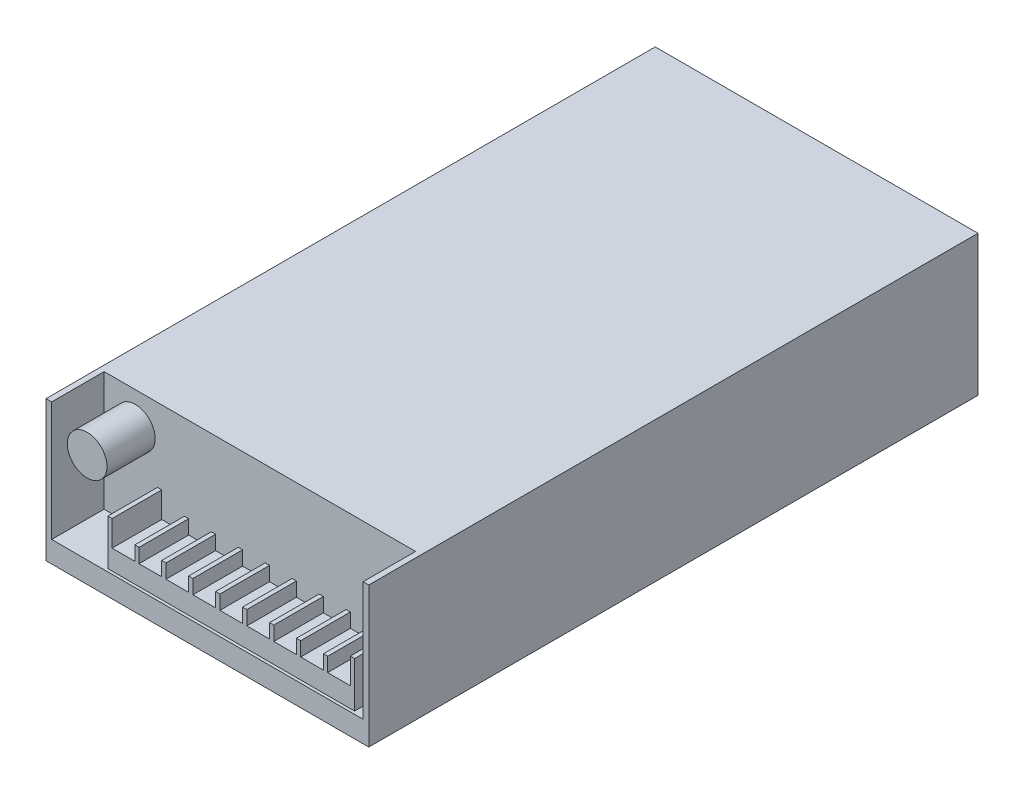
SolidWorks part; units mm, degrees
ref_plane "Front Plane" through (0, 0, 0) normal (0, 0, 1) x (1, 0, 0)
ref_plane "Top Plane" through (0, 0, 0) normal (0, 1, 0) x (1, 0, 0)
ref_plane "Right Plane" through (0, 0, 0) normal (1, 0, 0) x (0, 0, -1)
sketch "Sketch1" plane through (0, 0, 0) normal (0, 1, 0) x (1, 0, 0)
  line L1 (56.9, 107.4) -> (-56.9, 107.4)
  line L2 (56.9, 107.4) -> (56.9, -107.4)
  line L3 (56.9, -107.4) -> (-56.9, -107.4)
  line L4 (-56.9, 107.4) -> (-56.9, -107.4)
  line L5 (56.9, 107.4) -> (-56.9, -107.4) construction
  line L6 (56.9, -107.4) -> (-56.9, 107.4) construction
  point P0 (0, 0)
extrude "Boss-Extrude1" add sketch "Sketch1" along normal blind 49.5
sketch "Sketch2" plane through (0, 49.5, 0) normal (0, 1, 0) x (1, 0, 0)
  line L0 (54.9, -107.4) -> (54.9, -88.9)
  line L1 (-56.9, -107.4) -> (56.9, -107.4) construction
  line L2 (56.9, -107.4) -> (56.9, 107.4) construction
  line L3 (54.9, -88.9) -> (-54.9, -88.9)
  line L4 (-54.9, -88.9) -> (-54.9, -107.4)
  line L5 (-56.9, 107.4) -> (-56.9, -107.4) construction
  line L6 (-54.9, -107.4) -> (54.9, -107.4)
  dimension "D1" = 2
  dimension "D2" = 2
extrude "Cut-Extrude1" cut sketch "Sketch2" against normal blind 42
sketch "Sketch3" plane through (0, 7.5, 0) normal (0, 1, 0) x (1, 0, 0)
  line L0 (54.9, -88.9) -> (50.9, -88.9) construction
  line L1 (54.9, -88.9) -> (-54.9, -88.9) construction
  line L2 (50.9, -88.9) -> (50.9, -106.4)
  line L3 (50.9, -106.4) -> (-36.1, -106.4)
  line L4 (-36.1, -106.4) -> (-36.1, -88.9)
  line L5 (-36.1, -88.9) -> (50.9, -88.9)
  line L6 (-54.9, -107.4) -> (54.9, -107.4) construction
  line L7 (54.9, -107.4) -> (54.9, -88.9) construction
  dimension "D1" = 1
  dimension "D2" = 4
extrude "Boss-Extrude2" add sketch "Sketch3" along normal blind 7
sketch "Sketch4" plane through (0, 14.5, 0) normal (0, 1, 0) x (1, 0, 0)
  line L0 (-36.1, -88.9) -> (-36.1, -106.4)
  line L1 (-36.1, -106.4) -> (-34.6, -106.4)
  line L2 (-36.1, -106.4) -> (50.9, -106.4) construction
  line L3 (-34.6, -106.4) -> (-34.6, -88.9)
  line L4 (50.9, -88.9) -> (-36.1, -88.9) construction
  line L5 (-34.6, -88.9) -> (-36.1, -88.9)
  line L6 (-25.1, -88.9) -> (-26.6, -88.9)
  line L7 (-26.6, -88.9) -> (-26.6, -106.4)
  line L8 (-26.6, -106.4) -> (-25.1, -106.4)
  line L9 (-25.1, -106.4) -> (-25.1, -88.9)
  line L10 (-15.6, -88.9) -> (-17.1, -88.9)
  line L11 (-17.1, -88.9) -> (-17.1, -106.4)
  line L12 (-17.1, -106.4) -> (-15.6, -106.4)
  line L13 (-15.6, -106.4) -> (-15.6, -88.9)
  line L14 (-6.1, -88.9) -> (-7.6, -88.9)
  line L15 (-7.6, -88.9) -> (-7.6, -106.4)
  line L16 (-7.6, -106.4) -> (-6.1, -106.4)
  line L17 (-6.1, -106.4) -> (-6.1, -88.9)
  line L18 (3.4, -88.9) -> (1.9, -88.9)
  line L19 (1.9, -88.9) -> (1.9, -106.4)
  line L20 (1.9, -106.4) -> (3.4, -106.4)
  line L21 (3.4, -106.4) -> (3.4, -88.9)
  line L22 (12.9, -88.9) -> (11.4, -88.9)
  line L23 (11.4, -88.9) -> (11.4, -106.4)
  line L24 (11.4, -106.4) -> (12.9, -106.4)
  line L25 (12.9, -106.4) -> (12.9, -88.9)
  line L26 (22.4, -88.9) -> (20.9, -88.9)
  line L27 (20.9, -88.9) -> (20.9, -106.4)
  line L28 (20.9, -106.4) -> (22.4, -106.4)
  line L29 (22.4, -106.4) -> (22.4, -88.9)
  line L30 (31.9, -88.9) -> (30.4, -88.9)
  line L31 (30.4, -88.9) -> (30.4, -106.4)
  line L32 (30.4, -106.4) -> (31.9, -106.4)
  line L33 (31.9, -106.4) -> (31.9, -88.9)
  line L34 (41.4, -88.9) -> (39.9, -88.9)
  line L35 (39.9, -88.9) -> (39.9, -106.4)
  line L36 (39.9, -106.4) -> (41.4, -106.4)
  line L37 (41.4, -106.4) -> (41.4, -88.9)
  line L38 (50.9, -88.9) -> (49.4, -88.9)
  line L39 (49.4, -88.9) -> (49.4, -106.4)
  line L40 (49.4, -106.4) -> (50.9, -106.4)
  line L41 (50.9, -106.4) -> (50.9, -88.9)
  point P4 (0, 0)
  dimension "D1" = 1.5
  dimension "D2" = 10
extrude "Boss-Extrude3" add sketch "Sketch4" along normal blind 9.05 contours L0 L1 L3 L5 | L41 L38 L39 L40
extrude "Boss-Extrude4" add sketch "Sketch4<3>" along normal blind 5 contours L7 L8 L9 L6 | L11 L12 L13 L10 | L17 L14 L15 L16 | L21 L18 L19 L20 | L23 L24 L25 L22 | L27 L28 L29 L26 | L31 L32 L33 L30 | L35 L36 L37 L34
sketch "Sketch4<3>" plane through (0, 14.5, 0) normal (0, 1, 0) x (1, 0, 0) same geometry as "Sketch4"
sketch "Sketch5" plane through (0, 0, 88.9) normal (0, 0, 1) x (1, 0, 0)
  line L0 (-54.9, 38) -> (-50.9, 38) construction
  line L1 (-54.9, 7.5) -> (-54.9, 49.5) construction
  line L2 (-43.9, 49.5) -> (-43.9, 45) construction
  line L4 (54.9, 49.5) -> (-54.9, 49.5) construction
  circle A0 centre (-43.9, 38) radius 7
  point P10 (0, 0)
  point P11 (0, 0)
  point P12 (0, 0)
  point P13 (0, 0)
  dimension "D1" = 14
  dimension "D2" = 4.5
  dimension "D3" = 4
extrude "Boss-Extrude5" add sketch "Sketch5" along normal blind 17
sketch "Sketch6" plane through (0, 0, 0) normal (0, -1, 0) x (-1, 0, 0)
  line L0 (47.4, 97.4) -> (-47.8, 97.4) construction
  line L1 (-47.8, 97.4) -> (-47.8, -80.6) construction
  line L2 (-47.8, 97.4) -> (-47.8, 107.4) construction
  line L4 (-56.9, 107.4) -> (56.9, 107.4) construction
  line L5 (47.4, 97.4) -> (47.4, -80.6) construction
  line L6 (47.4, -80.6) -> (-47.8, -80.6) construction
  circle A0 centre (-47.8, -80.6) radius 1.5
  circle A1 centre (-47.8, 97.4) radius 1.5
  circle A2 centre (47.4, 97.4) radius 1.5
  circle A3 centre (47.4, -80.6) radius 1.5
extrude "Cut-Extrude2" cut sketch "Sketch6" against normal blind 5
